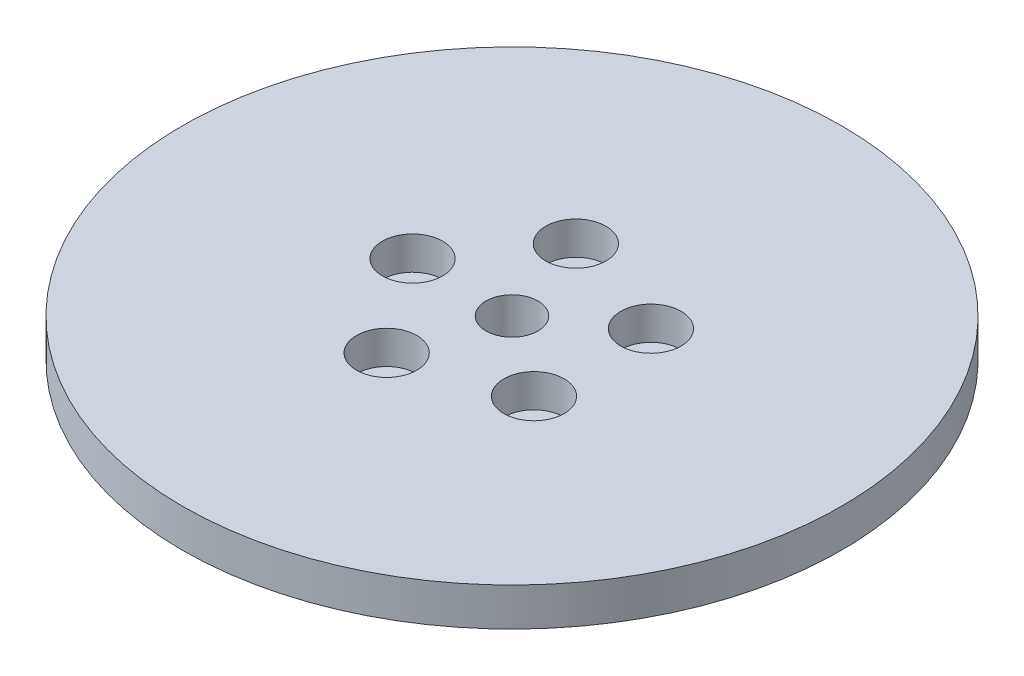
SolidWorks part; units mm, degrees
ref_plane "Front Plane" through (0, 0, 0) normal (0, 0, 1) x (1, 0, 0)
ref_plane "Top Plane" through (0, 0, 0) normal (0, 1, 0) x (1, 0, 0)
ref_plane "Right Plane" through (0, 0, 0) normal (1, 0, 0) x (0, 0, -1)
sketch "Sketch1" plane through (0, 0, 0) normal (0, 1, 0) x (1, 0, 0)
  circle A0 centre (0, 0) radius 95
  dimension "FLANGE_OD" = 190
extrude "Boss-Extrude1" add sketch "Sketch1" along normal blind 11
sketch "Sketch2" plane through (0, 0, 0) normal (0, 1, 0) x (1, 0, 0)
  circle A0 centre (0, 0) radius 7.5
  dimension "BORE_D" = 15
extrude "Cut-Extrude1" cut sketch "Sketch2" along normal through all
sketch "Sketch3" plane through (0, 11, 0) normal (0, 1, 0) x (1, 0, 0)
  circle A0 centre (0, 0) radius 28.6736 construction
  circle A1 centre (-28.6736, 0) radius 8.6907
  dimension "BOLT_D" = 17.3813
  dimension "BOLT_PCD" = 57.3472
extrude "Cut-Extrude2" cut sketch "Sketch3" against normal blind 9.5585
pattern_circular "CirPattern1" count 5 over 360 about axis through (0, 0, 0) along (0, 1, 0) of "Cut-Extrude2"
